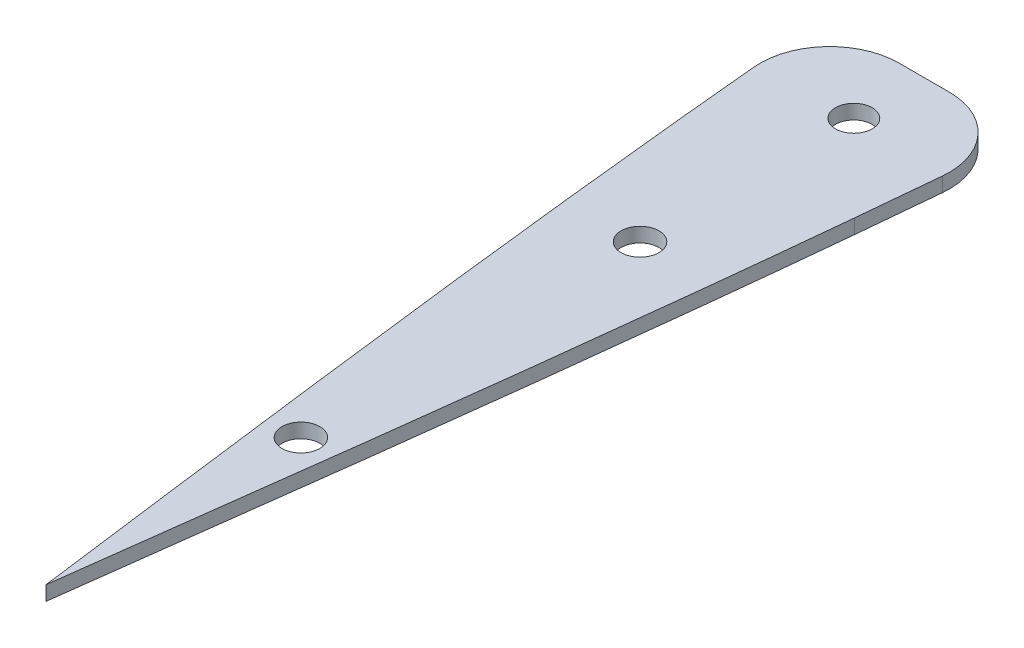
SolidWorks part; units mm, degrees
material "Balsa"
ref_plane "Front Plane" through (0, 0, 0) normal (0, 0, 1) x (1, 0, 0)
ref_plane "Top Plane" through (0, 0, 0) normal (0, 1, 0) x (1, 0, 0)
ref_plane "Right Plane" through (0, 0, 0) normal (1, 0, 0) x (0, 0, -1)
sketch "Sketch1" plane through (0, 0, 0) normal (0, 1, 0) x (1, 0, 0)
  line L0 (1.1081, 1.7265) -> (-45.0799, 1.7265) construction
  line L1 (-45.0799, 1.7265) -> (-45.0799, -11.2275) construction
  line L2 (-45.0799, -11.2275) -> (43.7517, -11.2275) construction
  line L3 (1.1081, 103.3269) -> (1.1081, -99.8738) construction
  line L4 (-45.0799, -11.2275) -> (-45.0799, -20.7525) construction
  line L5 (-28.2049, 1.7265) -> (-28.2049, -3.6075) construction
  line L6 (-9.9553, -3.6075) -> (-6.7697, -3.6075)
  line L7 (-28.2049, -3.6075) -> (-9.9553, -3.6075) construction
  line L8 (-6.7697, -3.6075) -> (1.1081, -3.6075) construction
  line L9 (8.9859, -3.6075) -> (12.1715, -3.6075)
  line L10 (12.1715, -3.6075) -> (18.1346, -3.6075) construction
  line L11 (12.1715, -3.6075) -> (18.1346, -3.6075) construction
  line L12 (18.1346, -3.6075) -> (29.3788, -3.6075) construction
  line L13 (1.1081, -3.6075) -> (8.9859, -3.6075) construction
  line L14 (-6.7697, -3.6075) -> (8.9859, -3.6075)
  circle A0 centre (1.1081, -11.3265) radius 2.013 construction
  circle A1 centre (1.1081, -11.3265) radius 2.013
  spline S0 degree 3 poles (1.1081, -99.8738) (4.5273, -73.5318) (7.9866, -47.1872) (10.6029, -20.7525) knots 0 0 0 0 0.38497 0.38497 0.38497 0.38497
  spline S3 degree 3 poles (1.1081, -99.8738) (-2.3112, -73.5318) (-5.7704, -47.1872) (-8.3867, -20.7525) knots 0 0 0 0 0.38497 0.38497 0.38497 0.38497
  spline S4 degree 3 poles (10.6029, -20.7525) (11.1, -15.7302) (11.6306, -10.016) (12.114, -4.2968) (12.1715, -3.6075) knots 0.38497 0.38497 0.38497 0.38497 0.458109 0.468132 0.468132 0.468132 0.468132
  spline S5 degree 3 poles (-8.3867, -20.7525) (-8.8838, -15.7302) (-9.4144, -10.016) (-9.8978, -4.2968) (-9.9553, -3.6075) knots 0.38497 0.38497 0.38497 0.38497 0.458109 0.468132 0.468132 0.468132 0.468132
  spline S8 degree 3 poles (12.1715, -3.6075) (12.8364, 4.367) (14.1908, 23.6726) (14.0058, 48.0803) (13.0188, 67.5796) (11.3266, 78.9472) (9.5869, 86.9693) (8.1237, 93.6397) (6.4505, 97.563) (4.8164, 101.3994) (2.3437, 102.5279) (1.1081, 103.3269) knots 0.468132 0.468132 0.468132 0.468132 0.584075 0.748482 0.821537 0.866809 0.914778 0.94069 0.965303 0.976863 1 1 1 1 construction
  spline S9 degree 3 poles (1.1081, 99.6196) (1.2739, 99.518) (1.6209, 99.2976) (2.0134, 99.0137) (2.3095, 98.7539) (2.4667, 98.5788) (2.6076, 98.3713) (2.8163, 97.9774) (3.0534, 97.4394) (3.4327, 96.5453) (3.8774, 95.496) (4.541, 93.8448) (5.2023, 91.9048) (5.8236, 89.3366) (6.4213, 86.5662) (7.0145, 83.8293) (7.767, 80.1951) (8.6007, 75.6781) (9.6391, 68.4081) (10.3034, 59.2354) (10.6788, 47.9926) (10.8555, 36.7918) (10.7415, 25.5951) (10.3009, 14.4244) (9.6564, 4.6878) (9.1767, -1.3266) (8.9859, -3.6075) knots 0.118744 0.118744 0.118744 0.118744 0.122149 0.125554 0.12896 0.132365 0.13577 0.139175 0.142581 0.145986 0.152796 0.159607 0.173228 0.186849 0.20047 0.214091 0.227711 0.254953 0.282195 0.336679 0.391163 0.445646 0.50013 0.554614 0.609098 0.642376 0.642376 0.642376 0.642376 construction
  spline S10 degree 3 poles (-7.1984, 1.7265) (-7.237, 2.2289) (-7.5577, 6.4638) (-8.0847, 14.4244) (-8.5253, 25.5951) (-8.6393, 36.7918) (-8.4626, 47.9926) (-8.0872, 59.2354) (-7.4229, 68.4081) (-6.3845, 75.6781) (-5.5508, 80.1951) (-4.7983, 83.8293) (-4.2051, 86.5662) (-3.6074, 89.3366) (-2.9861, 91.9048) (-2.3248, 93.8448) (-1.6612, 95.496) (-1.2165, 96.5453) (-0.8372, 97.4394) (-0.6001, 97.9774) (-0.3914, 98.3713) (-0.2505, 98.5788) (-0.0933, 98.7539) (0.2028, 99.0137) (0.5953, 99.2976) (0.9423, 99.518) (1.1081, 99.6196) knots 0.492798 0.492798 0.492798 0.492798 0.50013 0.554614 0.609098 0.663581 0.718065 0.772549 0.827033 0.854275 0.881516 0.895137 0.908758 0.922379 0.936 0.949621 0.956432 0.963242 0.966647 0.970053 0.973458 0.976863 0.980268 0.983674 0.987079 0.990484 0.990484 0.990484 0.990484 construction
  spline S11 degree 3 poles (-10.3826, 1.7265) (-10.8572, 7.9268) (-11.9611, 25.4575) (-11.7896, 48.0803) (-10.8026, 67.5796) (-9.1104, 78.9472) (-7.3707, 86.9693) (-5.9075, 93.6397) (-4.2343, 97.563) (-2.6002, 101.3994) (-0.1276, 102.5279) (1.1081, 103.3269) knots 0.493976 0.493976 0.493976 0.493976 0.584075 0.748482 0.821537 0.866809 0.914778 0.94069 0.965303 0.976863 1 1 1 1 construction
  spline S12 degree 3 poles (-9.9553, -3.6075) (-10.1035, -1.8299) (-10.2465, -0.0519) (-10.3826, 1.7265) knots 0.468132 0.468132 0.468132 0.468132 0.493976 0.493976 0.493976 0.493976 construction
  spline S13 degree 3 poles (-6.7697, -3.6075) (-6.9185, -1.8292) (-7.0618, -0.0511) (-7.1984, 1.7265) knots 0.466852 0.466852 0.466852 0.466852 0.492798 0.492798 0.492798 0.492798 construction
  dimension "D4" = 4.0259
  dimension "D1" = 12.954
  dimension "D2" = 9.525
  dimension "D3" = 5.334
extrude "Boss-Extrude1" add sketch "Sketch1" along normal blind 169.8727
sketch "Sketch2" plane through (0, 169.8727, 0) normal (0, 1, 0) x (1, 0, 0)
  line L1 (-9.9553, -3.6075) -> (25.8085, -3.6075)
  line L2 (-9.9553, -3.6075) -> (-9.9553, -26.3125)
  line L3 (-9.9553, -26.3125) -> (25.8085, -26.3125)
  line L4 (25.8085, -3.6075) -> (25.8085, -26.3125)
  circle A0 centre (1.1081, -11.3265) radius 2.0129 construction
  dimension "D1" = 14.986
extrude "Cut-Extrude1" cut sketch "Sketch2" against normal blind 23.0581
extrude "Cut-Extrude2" cut sketch "Sketch2<2>" along normal blind 23.0581 from surface starting at face at (-1.1046, 0, 29.7187)
sketch "Sketch2<2>" plane through (0, 169.8727, 0) normal (0, 1, 0) x (1, 0, 0) same geometry as "Sketch2"
fillet "Fillet1" radius 7.62 6 edges at (-7.8242, 11.5291, 26.3125) (10.0403, 11.5291, 26.3125) (12.1715, 84.9363, 3.6075) (-7.8242, 158.3436, 26.3125) (10.0403, 158.3436, 26.3125)
sketch "Sketch6" plane through (0, 0, 0) normal (0, -1, 0) x (1, 0, 0)
  line L0 (1.1081, 3.6075) -> (1.1081, 99.8738) construction
  line L1 (-1.6395, 3.6075) -> (3.8557, 3.6075) construction
  line L2 (-6.9254, 34.7606) -> (9.1416, 34.7606) construction
  circle A0 centre (1.1081, 71.9338) radius 2.075
  circle A1 centre (1.1081, 34.7606) radius 2.075
  dimension "D1" = 4.15
  dimension "D2" = 27.94
extrude "Cut-Extrude3" cut sketch "Sketch6" against normal through all both and the other way through all
sketch "Sketch7" plane through (0, 0, 0) normal (1, 0, 0) x (0, 0, -1)
  line L0 (-3.6075, 146.8145) -> (-3.6075, 23.0581) construction
  line L1 (-99.8738, 0) -> (-3.6075, 0)
  line L2 (-99.8738, 0) -> (-99.8738, 127.9186)
  line L3 (-99.8738, 127.9186) -> (-3.6075, 127.9186)
  line L4 (-3.6075, 0) -> (-3.6075, 127.9186)
  line L5 (-11.9209, 146.8145) -> (-20.7525, 146.8145) construction
  line L6 (-99.8738, 169.8727) -> (-3.6075, 169.8727)
  line L7 (-99.8738, 169.8727) -> (-99.8738, 129.5061)
  line L8 (-99.8738, 129.5061) -> (-3.6075, 129.5061)
  line L9 (-3.6075, 169.8727) -> (-3.6075, 129.5061)
  dimension "D1" = 17.3084
  dimension "D2" = 1.5875
extrude "Cut-Extrude4" cut sketch "Sketch7" against normal through all both and the other way through all
